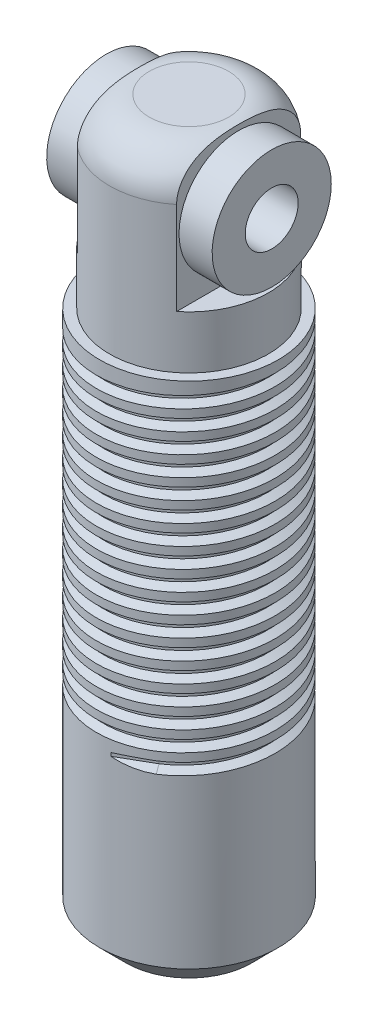
SolidWorks part; units mm, degrees
ref_plane "Front Plane" through (0, 0, 0) normal (0, 0, 1) x (1, 0, 0)
ref_plane "Top Plane" through (0, 0, 0) normal (0, 1, 0) x (1, 0, 0)
ref_plane "Right Plane" through (0, 0, 0) normal (1, 0, 0) x (0, 0, -1)
sketch "Sketch1" plane through (0, 0, 0) normal (0, 1, 0) x (1, 0, 0)
  circle A0 centre (0, 0) radius 12
  dimension "D1" = 24
extrude "Boss-Extrude1" add sketch "Sketch1" along normal blind 108.93
fillet "Fillet1" radius 6 1 edges at (0, 108.93, 12)
sketch "Sketch2" plane through (0, 0, 0) normal (0, 0, 1) x (1, 0, 0)
  line L0 (0, 108.93) -> (0, 0) construction
  line L1 (6, 108.93) -> (-6, 108.93) construction
  line L2 (-7.5, 88.93) -> (-22.0768, 88.93)
  line L3 (7.5, 108.93) -> (22.0768, 108.93)
  line L4 (7.5, 108.93) -> (7.5, 88.93)
  line L5 (7.5, 88.93) -> (22.0768, 88.93)
  line L6 (22.0768, 108.93) -> (22.0768, 88.93)
  line L7 (-22.0768, 108.93) -> (-22.0768, 88.93)
  line L8 (-7.5, 108.93) -> (-22.0768, 108.93)
  line L9 (-7.5, 108.93) -> (-7.5, 88.93)
  dimension "D1" = 20
  dimension "D2" = 15
extrude "Cut-Extrude1" cut sketch "Sketch2" against normal through all both and the other way through all
sketch "Sketch3" plane through (7.5, 0, 0) normal (1, 0, 0) x (0, 0, -1)
  line L0 (0, 108.93) -> (0, 0) construction
  line L1 (6, 108.93) -> (-6, 108.93) construction
  circle A0 centre (0, 98.93) radius 4
  dimension "D1" = 8
  dimension "D2" = 10
extrude "Cut-Extrude2" cut sketch "Sketch3" against normal through all both and the other way through all
sketch "Sketch4" plane through (0, 0, 0) normal (1, 0, 0) x (0, 0, -1)
  circle A0 centre (0, 98.93) radius 9
  circle A1 centre (0, 98.93) radius 4 construction
  circle A2 centre (0, 98.93) radius 4
  dimension "D1" = 18
extrude "Boss-Extrude2" add sketch "Sketch4" along normal mid plane 25
sketch "Sketch5" plane through (0, 0, 0) normal (0, -1, 0) x (1, 0, 0)
  circle A0 centre (0, 0) radius 13.5
  dimension "D1" = 27
extrude "Boss-Extrude3" add sketch "Sketch5" against normal blind 80.93
thread "Thread1" pitch 2 method cut profile "Thread Profile1" start angle 0, offset 0, length 50, pitch 3, diameter 27
ref_plane "Plane1" through (-13.5, 80.93, 0) normal (0, 0, 1) x (-1, 0, 0)
sketch "Thread Profile1" plane through (-13.5, 80.93, 0) normal (0, 0, 1) x (-1, 0, 0)
  line L0 (0, 0) -> (0, 2) construction
  line L11 (0, 0) -> (0, 1.75)
  line L12 (0, 1.75) -> (-1.0825, 1.125)
  line L13 (-1.0825, 1.125) -> (-1.0825, 0.625)
  line L15 (-1.0825, 0.625) -> (0, 0)
  line L17 (-1.0825, 0.875) -> (0, 0.875) construction
  point P2 (0, 0)
  dimension "Pitch" = 2
  dimension "Profile_Angle" = 60
  dimension "Profile_Land" = 0.5
  dimension "Profile_Height" = 1.0825
sketch "Sketch13" plane through (0, 0, 0) normal (0, 0, -1) x (-1, 0, 0)
  line L4 (13.5, 80.93) -> (12.4175, 80.305)
  line L5 (12.4175, 80.305) -> (12.4175, 79.805)
  line L6 (12.4175, 79.805) -> (13.5, 79.18)
  line L7 (13.5, 79.18) -> (13.5, 80.93)
  line L8 (13.5, 80.93) -> (12.4175, 80.305)
  line L9 (12.4175, 80.305) -> (12.4175, 79.805)
  line L10 (12.4175, 79.805) -> (13.5, 79.18)
  line L11 (13.5, 79.18) -> (13.5, 80.93)
  dimension "D1" = 0
extrude "Cut-Extrude3" cut sketch "Sketch13" along normal blind 0.93 and the other way through all
sketch "Sketch14" plane through (0, 0, 0) normal (0.866, 0, -0.5) x (-0.5, 0, -0.866)
  line L4 (-12.4175, 30.3042) -> (-13.5, 30.9292)
  line L5 (-13.5, 30.9292) -> (-13.5, 29.1792)
  line L6 (-13.5, 29.1792) -> (-12.4175, 29.8042)
  line L7 (-12.4175, 29.8042) -> (-12.4175, 30.3042)
  line L8 (-12.4175, 30.3042) -> (-13.5, 30.9292)
  line L9 (-13.5, 30.9292) -> (-13.5, 29.1792)
  line L10 (-13.5, 29.1792) -> (-12.4175, 29.8042)
  line L11 (-12.4175, 29.8042) -> (-12.4175, 30.3042)
  dimension "D1" = 0
extrude "Cut-Extrude4" cut sketch "Sketch14" against normal blind 20.93
sketch "Sketch15" plane through (0, 0, 0) normal (0, -1, 0) x (1, 0, 0)
  circle A0 centre (0, 0) radius 5
  dimension "D1" = 10
extrude "Cut-Extrude5" cut sketch "Sketch15" against normal blind 75
chamfer "Chamfer1" distance 4 angle 45 1 edges at (0, 0, -13.5)
